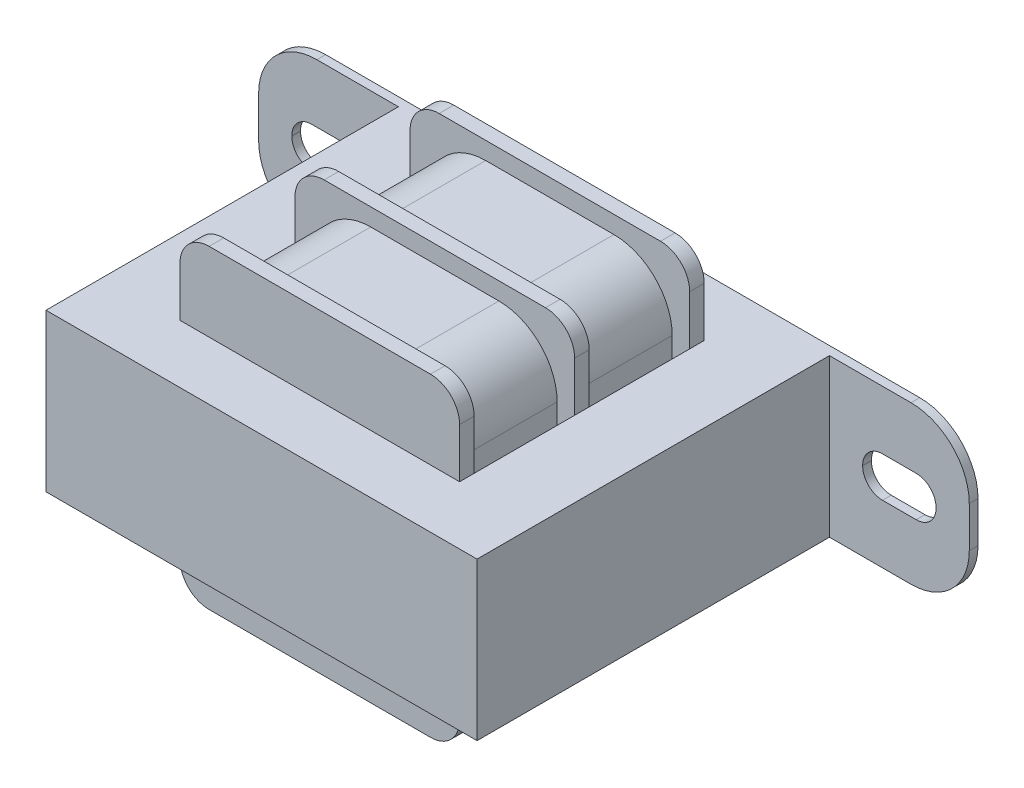
SolidWorks part; units mm, degrees
ref_plane "Front Plane" through (0, 0, 0) normal (0, 0, 1) x (1, 0, 0)
ref_plane "Top Plane" through (0, 0, 0) normal (0, 1, 0) x (1, 0, 0)
ref_plane "Right Plane" through (0, 0, 0) normal (1, 0, 0) x (0, 0, -1)
sketch "Sketch1" plane through (0, 0, 0) normal (0, 0, 1) x (1, 0, 0)
  line L1 (-18.5, 6.75) -> (18.5, 6.75)
  line L2 (-18.5, 6.75) -> (-18.5, -6.75)
  line L3 (-18.5, -6.75) -> (18.5, -6.75)
  line L4 (18.5, 6.75) -> (18.5, -6.75)
  line L5 (-18.5, 6.75) -> (18.5, -6.75) construction
  line L6 (-18.5, -6.75) -> (18.5, 6.75) construction
  point P0 (0, 0)
  dimension "D1" = 37
  dimension "D2" = 13.5
extrude "Boss-Extrude1" add sketch "Sketch1" along normal mid plane 31
sketch "Sketch2" plane through (0, 6.75, 0) normal (0, 1, 0) x (1, 0, 0)
  line L1 (12, -10.5) -> (-12, -10.5)
  line L2 (12, -10.5) -> (12, 10.5)
  line L3 (12, 10.5) -> (-12, 10.5)
  line L4 (-12, -10.5) -> (-12, 10.5)
  line L5 (12, -10.5) -> (-12, 10.5) construction
  line L6 (12, 10.5) -> (-12, -10.5) construction
  point P0 (0, 0)
  dimension "D1" = 21
  dimension "D2" = 24
extrude "Cut-Extrude1" cut sketch "Sketch2" against normal blind 31
sketch "Sketch3" plane through (0, 0, -10.5) normal (0, 0, 1) x (1, 0, 0)
  line L0 (-12, -6.75) -> (-12, 6.75) construction
  line L1 (12, -13.5) -> (-12, -13.5)
  line L2 (12, -13.5) -> (12, 13.5)
  line L3 (12, 13.5) -> (-12, 13.5)
  line L4 (-12, -13.5) -> (-12, 13.5)
  line L5 (12, -13.5) -> (-12, 13.5) construction
  line L6 (12, 13.5) -> (-12, -13.5) construction
  point P0 (0, 0)
  dimension "D1" = 27
extrude "Boss-Extrude2" add sketch "Sketch3" along normal blind 1.25
sketch "Sketch4" plane through (0, 0, 10.5) normal (0, 0, -1) x (-1, 0, 0)
  line L0 (12, -6.75) -> (12, 6.75) construction
  line L1 (12, 13.5) -> (-12, 13.5)
  line L2 (12, 13.5) -> (12, -13.5)
  line L3 (12, -13.5) -> (-12, -13.5)
  line L4 (-12, 13.5) -> (-12, -13.5)
  line L5 (12, 13.5) -> (-12, -13.5) construction
  line L6 (12, -13.5) -> (-12, 13.5) construction
  point P0 (0, 0)
  dimension "D1" = 27
extrude "Boss-Extrude3" add sketch "Sketch4" along normal blind 1.25
sketch "Sketch5" plane through (0, 0, 0) normal (0, 0, 1) x (1, 0, 0)
  line L1 (12, 13.5) -> (-12, 13.5)
  line L2 (12, 13.5) -> (12, -13.5)
  line L3 (12, -13.5) -> (-12, -13.5)
  line L4 (-12, 13.5) -> (-12, -13.5)
  line L5 (12, 13.5) -> (-12, -13.5) construction
  line L6 (12, -13.5) -> (-12, 13.5) construction
  line L7 (-12, -6.75) -> (-12, -13.5) construction
  point P0 (0, 0)
  dimension "D1" = 27
extrude "Boss-Extrude4" add sketch "Sketch5" along normal mid plane 1.25
sketch "Sketch6" plane through (0, 0, -10.5) normal (0, 0, -1) x (-1, 0, 0)
  line L0 (-12, -13.5) -> (-12, -11)
  line L1 (-12, -13.5) -> (-12, -6.75) construction
  line L2 (-12, -13.5) -> (-9.5, -13.5)
  line L3 (12, -13.5) -> (-12, -13.5) construction
  line L4 (12, -13.5) -> (12, -11)
  line L5 (12, -6.75) -> (12, -13.5) construction
  line L6 (12, -13.5) -> (9.5, -13.5)
  arc A0 (-12, -11) -> (-9.5, -13.5) centre (-9.5, -11) ccw
  arc A1 (12, -11) -> (9.5, -13.5) centre (9.5, -11) cw
  dimension "D1" = 2.5
  dimension "D2" = 2.5
  dimension "D3" = 2.5
  dimension "D4" = 2.5
extrude "Cut-Extrude2" cut sketch "Sketch6" against normal blind 30
sketch "Sketch7" plane through (0, 0, -10.5) normal (0, 0, -1) x (-1, 0, 0)
  line L0 (12, 13.5) -> (9.5, 13.5)
  line L1 (-12, 13.5) -> (12, 13.5) construction
  line L2 (12, 13.5) -> (12, 11)
  line L3 (12, 13.5) -> (12, 6.75) construction
  line L4 (-12, 13.5) -> (-12, 11)
  line L5 (-12, 6.75) -> (-12, 13.5) construction
  line L6 (-12, 13.5) -> (-9.5, 13.5)
  arc A0 (9.5, 13.5) -> (12, 11) centre (9.5, 11) cw
  arc A1 (-9.5, 13.5) -> (-12, 11) centre (-9.5, 11) ccw
  dimension "D1" = 2.5
  dimension "D2" = 2.5
  dimension "D3" = 2.5
  dimension "D4" = 2.5
extrude "Cut-Extrude3" cut sketch "Sketch7" against normal blind 30
sketch "Sketch8" plane through (0, 0, 0) normal (0, 0, 1) x (1, 0, 0)
  line L1 (-5.5, 12) -> (5.5, 12)
  line L2 (-10.5, 7) -> (-10.5, -7)
  line L3 (-5.5, -12) -> (5.5, -12)
  line L4 (10.5, 7) -> (10.5, -7)
  line L5 (-10.5, 12) -> (10.5, -12) construction
  line L6 (-10.5, -12) -> (10.5, 12) construction
  arc A0 (5.5, 12) -> (10.5, 7) centre (5.5, 7) cw
  arc A1 (-5.5, 12) -> (-10.5, 7) centre (-5.5, 7) ccw
  arc A2 (5.5, -12) -> (10.5, -7) centre (5.5, -7) ccw
  arc A3 (-10.5, -7) -> (-5.5, -12) centre (-5.5, -7) ccw
  point P0 (0, 0)
  dimension "D3" = 5
  dimension "D1" = 21
  dimension "D2" = 24
extrude "Boss-Extrude5" add sketch "Sketch8" along normal mid plane 20
ref_plane "Plane1" through (0, 0, -15.5) normal (0, 0, -1) x (0, -1, 0)
sketch "Sketch9" plane through (0, 0, -15.5) normal (0, 0, -1) x (0, -1, 0)
  line L0 (6.75, 18.5) -> (6.75, -18.5) construction
  line L1 (-6.75, 18.5) -> (6.75, 18.5)
  line L2 (-6.75, 18.5) -> (-6.75, 30.5)
  line L3 (-6.75, 30.5) -> (6.75, 30.5)
  line L4 (6.75, 18.5) -> (6.75, 30.5)
  dimension "D1" = 12
extrude "Boss-Extrude6" add sketch "Sketch9" against normal blind 0.75
sketch "Sketch11" plane through (0, 0, -14.75) normal (0, 0, 1) x (1, 0, 0)
  line L0 (-24.5, 6.75) -> (-25.5, 6.75)
  line L1 (-30.5, 6.75) -> (-18.5, 6.75) construction
  line L2 (-30.5, 1.75) -> (-30.5, 0)
  line L3 (-30.5, -6.75) -> (-30.5, 6.75) construction
  line L4 (-30.5, 0) -> (-30.5, -1.75)
  line L5 (-25.5, -6.75) -> (-24.5, -6.75)
  line L6 (-18.5, -6.75) -> (-30.5, -6.75) construction
  arc A0 (-30.5, -1.75) -> (-25.5, -6.75) centre (-25.5, -1.75) ccw
  arc A1 (-25.5, 6.75) -> (-30.5, 1.75) centre (-25.5, 1.75) ccw
  point P15 (-30.5, -6.75)
  point P18 (-30.5, 6.75)
  dimension "D1" = 5
extrude "Cut-Extrude6" cut sketch "Sketch11" against normal blind 0.75 and the other way through all flip side to cut
sketch "Sketch14" plane through (0, 0, -14.75) normal (0, 0, 1) x (1, 0, 0)
  line L0 (-18.5, 0) -> (-30.5, 0) construction
  line L1 (-18.5, 6.75) -> (-18.5, -6.75) construction
  line L2 (-30.5, -1.75) -> (-30.5, 1.75) construction
  line L4 (-25.95, 1.725) -> (-23.05, 1.725)
  line L5 (-27.65, 0.025) -> (-27.65, -0.025)
  line L6 (-25.95, -1.725) -> (-23.05, -1.725)
  line L7 (-21.35, 0.025) -> (-21.35, -0.025)
  line L8 (-27.65, 1.725) -> (-21.35, -1.725) construction
  line L9 (-27.65, -1.725) -> (-21.35, 1.725) construction
  arc A0 (-23.05, 1.725) -> (-21.35, 0.025) centre (-23.05, 0.025) cw
  arc A1 (-23.05, -1.725) -> (-21.35, -0.025) centre (-23.05, -0.025) ccw
  arc A2 (-27.65, -0.025) -> (-25.95, -1.725) centre (-25.95, -0.025) ccw
  arc A3 (-25.95, 1.725) -> (-27.65, 0.025) centre (-25.95, 0.025) ccw
  point P6 (-24.5, 0)
  dimension "D3" = 1.7
  dimension "D1" = 3.45
  dimension "D2" = 6.3
extrude "Cut-Extrude7" cut sketch "Sketch14" against normal blind 0.75
ref_plane "Plane2" through (0, 0, -15.5) normal (0, 0, -1) x (0, 1, 0)
sketch "Sketch15" plane through (0, 0, -15.5) normal (0, 0, -1) x (0, 1, 0)
  line L0 (6.75, 18.5) -> (6.75, -25.5) construction
  line L1 (-6.75, 18.5) -> (6.75, 18.5)
  line L2 (-6.75, 18.5) -> (-6.75, 30.5)
  line L3 (-6.75, 30.5) -> (6.75, 30.5)
  line L4 (6.75, 18.5) -> (6.75, 30.5)
  dimension "D1" = 12
extrude "Boss-Extrude7" add sketch "Sketch15" against normal blind 0.75
sketch "Sketch16" plane through (0, 0, -14.75) normal (0, 0, 1) x (1, 0, 0)
  line L0 (24.5, -6.75) -> (25.5, -6.75)
  line L1 (30.5, -6.75) -> (18.5, -6.75) construction
  line L2 (30.5, -1.75) -> (30.5, 1.75)
  line L3 (30.5, 6.75) -> (30.5, -6.75) construction
  line L4 (25.5, 6.75) -> (24.5, 6.75)
  line L5 (18.5, 6.75) -> (30.5, 6.75) construction
  arc A0 (30.5, 1.75) -> (25.5, 6.75) centre (25.5, 1.75) ccw
  arc A1 (25.5, -6.75) -> (30.5, -1.75) centre (25.5, -1.75) ccw
  point P13 (30.5, 6.75)
  point P16 (30.5, -6.75)
  dimension "D1" = 5
extrude "Cut-Extrude8" cut sketch "Sketch16" against normal blind 0.75 and the other way through all flip side to cut
sketch "Sketch18" plane through (0, 0, -14.75) normal (0, 0, 1) x (1, 0, 0)
  line L0 (18.5, 0) -> (30.5, 0) construction
  line L1 (18.5, -6.75) -> (18.5, 6.75) construction
  line L2 (30.5, 1.75) -> (30.5, -1.75) construction
  line L4 (23.05, 1.725) -> (25.95, 1.725)
  line L5 (21.35, 0.025) -> (21.35, -0.025)
  line L6 (23.05, -1.725) -> (25.95, -1.725)
  line L7 (27.65, 0.025) -> (27.65, -0.025)
  line L8 (21.35, 1.725) -> (27.65, -1.725) construction
  line L9 (21.35, -1.725) -> (27.65, 1.725) construction
  arc A0 (23.05, 1.725) -> (21.35, 0.025) centre (23.05, 0.025) ccw
  arc A1 (21.35, -0.025) -> (23.05, -1.725) centre (23.05, -0.025) ccw
  arc A2 (25.95, -1.725) -> (27.65, -0.025) centre (25.95, -0.025) ccw
  arc A3 (25.95, 1.725) -> (27.65, 0.025) centre (25.95, 0.025) cw
  point P7 (24.5, 0)
  dimension "D3" = 1.7
  dimension "D1" = 6.3
  dimension "D2" = 3.45
extrude "Cut-Extrude9" cut sketch "Sketch18" against normal blind 0.75
